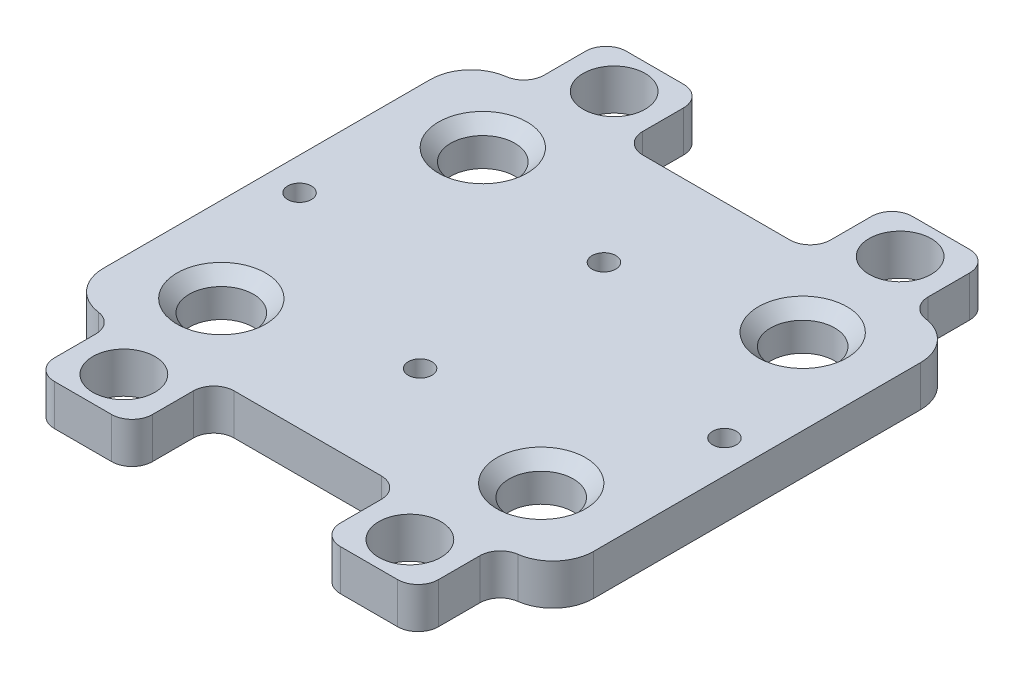
SolidWorks part; units mm, degrees
ref_plane "Front Plane" through (0, 0, 0) normal (0, 0, 1) x (1, 0, 0)
ref_plane "Top Plane" through (0, 0, 0) normal (0, 1, 0) x (1, 0, 0)
ref_plane "Right Plane" through (0, 0, 0) normal (1, 0, 0) x (0, 0, -1)
sketch "Sketch1" plane through (0, 0, 0) normal (1, 0, 0) x (0, 0, -1)
  line L1 (0, 0) -> (50, 0)
  line L2 (0, 0) -> (0, 5)
  line L3 (0, 5) -> (50, 5)
  line L4 (50, 0) -> (50, 5)
  dimension "D1" = 50
  dimension "D2" = 5
extrude "Boss-Extrude1" add sketch "Sketch1" along normal blind 60
sketch "Sketch2" plane through (0, 5, 0) normal (0, 1, 0) x (1, 0, 0)
  line L0 (60, 25) -> (0, 25) construction
  line L1 (60, 50) -> (60, 0) construction
  line L2 (0, 50) -> (0, 0) construction
  line L3 (41.5, 50) -> (41.5, 60)
  line L4 (30, 50) -> (30, 0) construction
  line L5 (60, 50) -> (0, 50) construction
  line L6 (60, 0) -> (0, 0) construction
  line L7 (6.5, 50) -> (18.5, 50)
  line L8 (6.5, 50) -> (6.5, 60)
  line L9 (6.5, 60) -> (18.5, 60)
  line L10 (18.5, 50) -> (18.5, 60)
  line L11 (53.5, 60) -> (41.5, 60)
  line L12 (53.5, 50) -> (53.5, 60)
  line L13 (53.5, 50) -> (41.5, 50)
  line L14 (53.5, 0) -> (41.5, 0)
  line L15 (53.5, 0) -> (53.5, -10)
  line L16 (53.5, -10) -> (41.5, -10)
  line L17 (18.5, 0) -> (18.5, -10)
  line L18 (6.5, -10) -> (18.5, -10)
  line L19 (6.5, 0) -> (6.5, -10)
  line L20 (6.5, 0) -> (18.5, 0)
  line L21 (41.5, 0) -> (41.5, -10)
  line L22 (12.5, 60) -> (12.5, 50) construction
  circle A0 centre (49.575, 41) radius 3.925
  circle A1 centre (10.425, 41) radius 3.925
  circle A2 centre (10.425, 9) radius 3.925
  circle A3 centre (49.575, 9) radius 3.925
  circle A5 centre (30, 36.25) radius 1.45
  circle A6 centre (30, 13.75) radius 1.45
  circle A7 centre (12.5, 55) radius 3.8
  circle A8 centre (47.5, 55) radius 3.8
  circle A9 centre (12.5, -5) radius 3.8
  circle A10 centre (47.5, -5) radius 3.8
  circle A11 centre (56, 25) radius 1.45
  circle A12 centre (4, 25) radius 1.45
  line M3 (0, 0) -> (60, 0)
  line M5 (60, 50) -> (0, 50)
  dimension "D2" = 7.85
  dimension "D5" = 2.9
  dimension "D6" = 2.9
  dimension "D12" = 7.6
  dimension "D9" = 2.9
  dimension "D1" = 16
  dimension "D7" = 11.25
  dimension "D8" = 11.25
  dimension "D4" = 4
  dimension "D10" = 10
  dimension "D11" = 12
  dimension "D3" = 5
  dimension "D13" = 6
  dimension "D14" = 12.5
extrude "Cut-Extrude1" cut sketch "Sketch2" against normal through all contours A0 | A11 | A6 | A3 | A2 | A12 | A1 | A5 region at (49.575, 5, -41) region at (10.425, 5, -9) region at (49.575, 5, -9) region at (30, 5, -13.75) region at (56, 5, -25) region at (4, 5, -25)
chamfer "Chamfer1" distance 1.5 angle 45 4 edges at (10.425, 5, -5.075) (49.575, 5, -5.075) (10.425, 5, -44.925) (49.575, 5, -37.075)
fillet "Fillet2" radius 5 4 edges at (0, 2.5, -50) (0, 2.5, 0) (60, 2.5, 0) (60, 2.5, -50)
extrude "Boss-Extrude2" add sketch "Sketch2<3>" against normal blind 5 contours L10 L9 L8 M5 | L12 L11 L3 M5 | L21 L16 L15 M3 | L19 L18 L17 M3 region at (41.6562, 5, -55) region at (12.5, 5, -50.1562) region at (53.3438, 5, 5) region at (18.3438, 5, 5)
sketch "Sketch2<3>" plane through (0, 5, 0) normal (0, 1, 0) x (1, 0, 0) same geometry as "Sketch2"
fillet "Fillet5" radius 2.5 8 edges at (41.5, 2.5, 10) (53.5, 2.5, 10) (6.5, 2.5, 10) (18.5, 2.5, 10) (53.5, 2.5, -60) (41.5, 2.5, -60) (6.5, 2.5, -60) (18.5, 2.5, -60)
fillet "Fillet6" radius 2.5 8 edges at (18.5, 2.5, 0) (53.5, 2.5, 0) (6.5, 2.5, 0) (41.5, 2.5, 0) (6.5, 2.5, -50) (41.5, 2.5, -50) (53.5, 2.5, -50) (18.5, 2.5, -50)
chamfer "Chamfer2" distance 1.5 angle 45 3 edges at (30, 0, -12.3) (56, 0, -23.55) (30, 0, -34.8)
chamfer "Chamfer3" distance 1.5 angle 45 1 edges at (4, 0, -23.55)
equation "\"width\"= 50"
equation "\"height\"= 5"
equation "\"D1@Sketch1\"=\"width\""
equation "\"D2@Sketch1\"=\"height\""
equation "\"D1@Boss-Extrude2\"=\"height\""
equation "\"height side thingies for axis\" = 10"
equation "\"width side thingies for axis\" = 12"
equation "\"height for circle\"= \"height side thingies for axis\" / 2"
equation "\"D10@Sketch2\"=\"height side thingies for axis\""
equation "\"D11@Sketch2\"=\"width side thingies for axis\""
equation "\"D3@Sketch2\"=\"height for circle\""
equation "\"width for circle\"= \"width side thingies for axis\" / 2"
equation "\"D13@Sketch2\"=\"width for circle\""
equation "\"width where side thing should be\"= \"width\" / 4"
equation "\"D14@Sketch2\"=\"width where side thing should be\""
